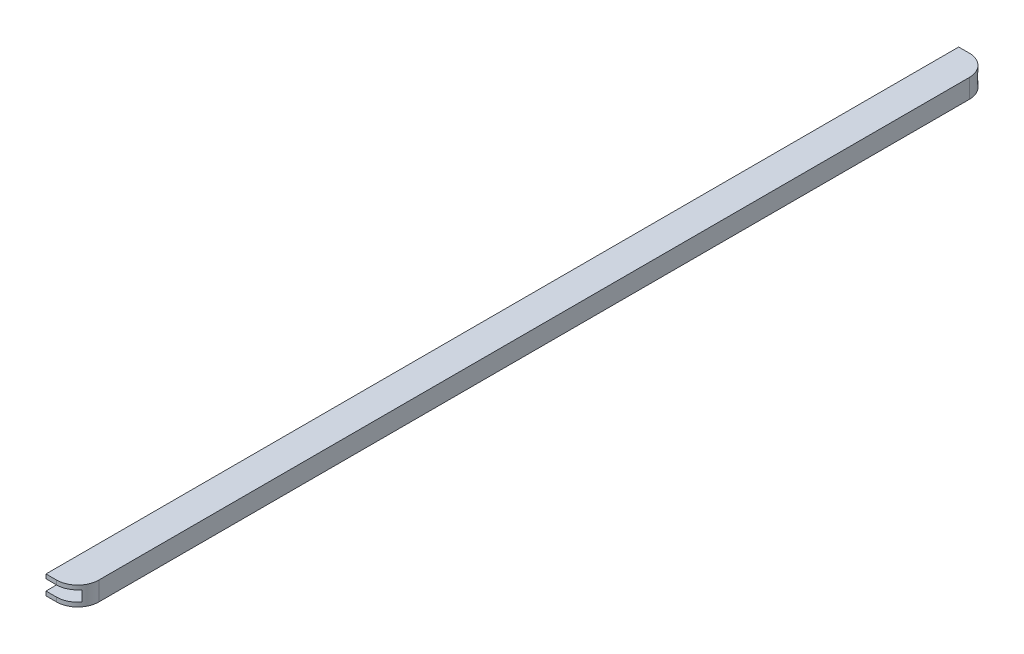
SolidWorks part; units mm, degrees
ref_plane "Front Plane" through (0, 0, 0) normal (0, 0, 1) x (1, 0, 0)
ref_plane "Top Plane" through (0, 0, 0) normal (0, 1, 0) x (1, 0, 0)
ref_plane "Right Plane" through (0, 0, 0) normal (1, 0, 0) x (0, 0, -1)
sketch "Sketch2" plane through (0, 0, 0) normal (0, 1, 0) x (1, 0, 0)
  line L1 (-83.1356, 45.3814) -> (-68.1356, 45.3814)
  line L2 (-83.1356, 45.3814) -> (-83.1356, -386.6186)
  line L3 (-83.1356, -386.6186) -> (-68.1356, -386.6186)
  line L4 (-68.1356, 45.3814) -> (-68.1356, -386.6186)
  dimension "D1" = 15
  dimension "D2" = 432
extrude "Boss-Extrude1" add sketch "Sketch2" along normal blind 9
sketch "Sketch3" plane through (-83.1356, 0, 0) normal (-1, 0, 0) x (0, 0, 1)
  line L0 (-45.3814, 0) -> (386.6186, 0) construction
  line L1 (-45.3814, 2) -> (386.6186, 2)
  line L2 (-45.3814, 2) -> (-45.3814, 7)
  line L3 (-45.3814, 7) -> (386.6186, 7)
  line L4 (386.6186, 2) -> (386.6186, 7)
  line L5 (-45.3814, 9) -> (386.6186, 9) construction
  line L6 (-45.3814, 9) -> (-45.3814, 0) construction
  line L7 (386.6186, 9) -> (386.6186, 0) construction
  dimension "D1" = 2
  dimension "D2" = 2
  dimension "D3" = 0
  dimension "D4" = 0
extrude "Cut-Extrude1" cut sketch "Sketch3" against normal blind 13
fillet "Fillet1" radius 10 1 edges at (-68.1356, 4.5, 386.6186)
fillet "Fillet2" radius 10 1 edges at (-68.1356, 4.5, -45.3814) type face fillet first side face at (-76.1356, 4.5, -45.3814) second side face at (-68.1356, 4.5, 165.6186)
